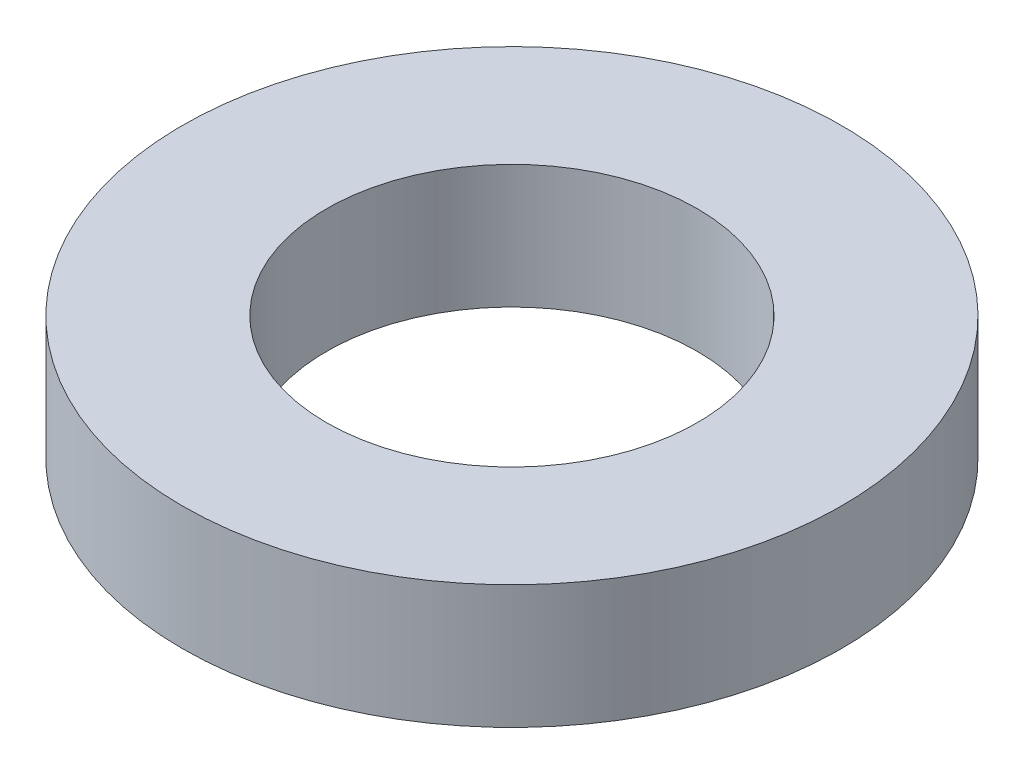
SolidWorks part; units mm, degrees
ref_plane "Front Plane" through (0, 0, 0) normal (0, 0, 1) x (1, 0, 0)
ref_plane "Top Plane" through (0, 0, 0) normal (0, 1, 0) x (1, 0, 0)
ref_plane "Right Plane" through (0, 0, 0) normal (1, 0, 0) x (0, 0, -1)
sketch "Sketch1" plane through (0, 0, 0) normal (0, 1, 0) x (1, 0, 0)
  circle A0 centre (0, 0) radius 80
  dimension "FLANGE_OD" = 160
extrude "Boss-Extrude1" add sketch "Sketch1" along normal blind 30
sketch "Sketch2" plane through (0, 0, 0) normal (0, 1, 0) x (1, 0, 0)
  circle A0 centre (0, 0) radius 45
  dimension "BORE_D" = 90
extrude "Cut-Extrude1" cut sketch "Sketch2" along normal through all
sketch "Sketch3" plane through (0, 30, 0) normal (0, 1, 0) x (1, 0, 0)
  circle A0 centre (0, 0) radius 33.9984 construction
  circle A1 centre (-33.9984, 0) radius 3.9641
  dimension "BOLT_D" = 7.9283
  dimension "BOLT_PCD" = 67.9968
extrude "Cut-Extrude2" cut sketch "Sketch3" against normal blind 29.5588 rebuild error yes
pattern_circular "CirPattern1" count 4 over 360 rebuild error yes
